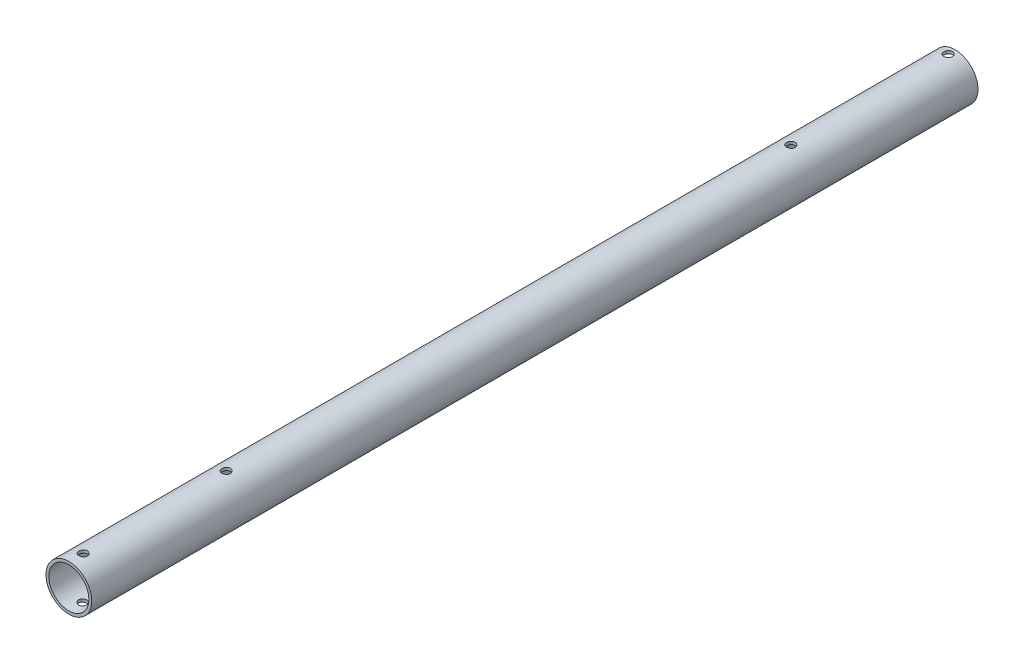
SolidWorks part; units mm, degrees
material "Hexcel AS4C (3000 Filaments)"
ref_plane "Front Plane" through (0, 0, 0) normal (0, 0, 1) x (1, 0, 0)
ref_plane "Top Plane" through (0, 0, 0) normal (0, 1, 0) x (1, 0, 0)
ref_plane "Right Plane" through (0, 0, 0) normal (1, 0, 0) x (0, 0, -1)
sketch "Sketch1" plane through (0, 0, 0) normal (0, 0, 1) x (1, 0, 0)
  circle A0 centre (0, 0) radius 7
  circle A1 centre (0, 0) radius 8
extrude "Boss-Extrude1" add sketch "Sketch1" along normal blind 310
sketch "Sketch2" plane through (0, -10, 0) normal (0, -1, 0) x (1, 0, 0)
  circle A1 centre (0, 57.5) radius 1.5
  circle A2 centre (0, 305) radius 1.5
  circle A3 centre (0, 255) radius 1.5
  circle A4 centre (0, 2.5) radius 1.5
extrude "Cut-Extrude2" cut sketch "Sketch2" against normal blind 20
